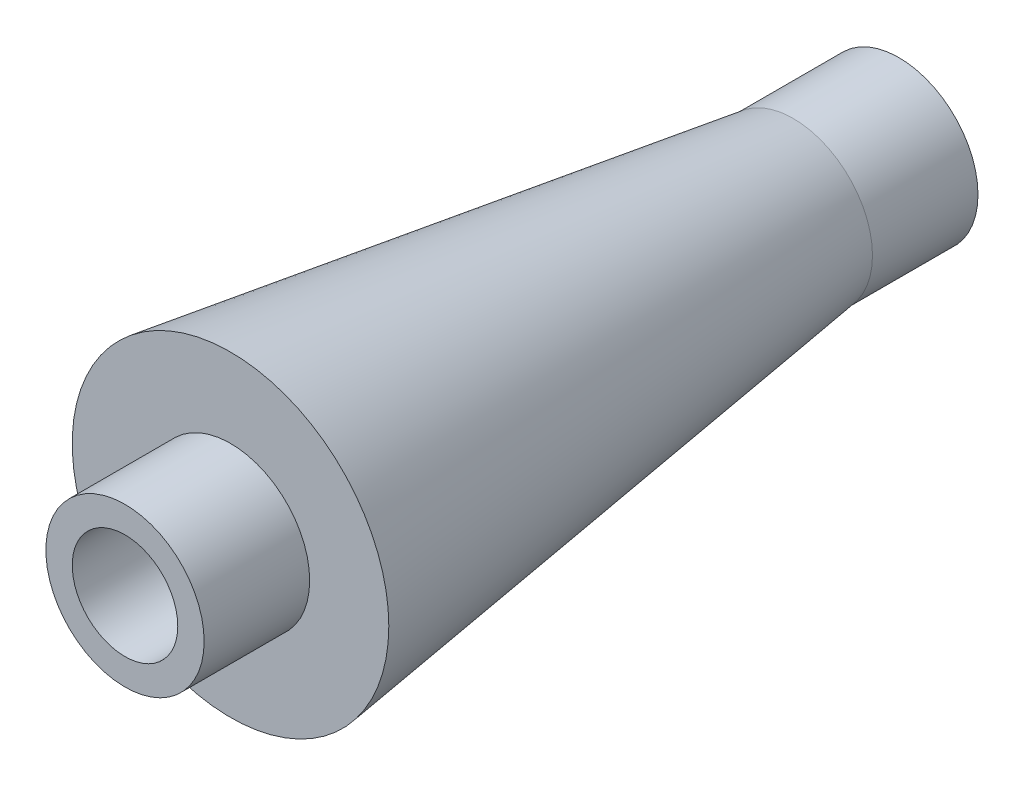
SolidWorks part; units mm, degrees
ref_plane "Front Plane" through (0, 0, 0) normal (0, 0, 1) x (1, 0, 0)
ref_plane "Top Plane" through (0, 0, 0) normal (0, 1, 0) x (1, 0, 0)
ref_plane "Right Plane" through (0, 0, 0) normal (1, 0, 0) x (0, 0, -1)
sketch "Sketch1" plane through (0, 0, 0) normal (0, 1, 0) x (1, 0, 0)
  line L0 (7.1438, 19.05) -> (7.1438, 9.525) construction
  line L1 (7.1438, 9.525) -> (-7.1438, 9.525) construction
  line L2 (14.2875, 19.05) -> (-14.2875, 19.05) construction
  line L3 (7.1437, 79.375) -> (-7.1437, 79.375) construction
  line L4 (7.1438, 69.85) -> (7.1437, 79.375) construction
  line L5 (7.1438, 69.85) -> (14.2875, 19.05) construction
  line L7 (7.1438, 19.05) -> (7.1438, 9.525)
  line L8 (7.1438, 9.525) -> (4.7625, 9.525)
  line L9 (14.2875, 19.05) -> (7.1438, 19.05)
  line L10 (7.1437, 79.375) -> (4.7625, 79.375)
  line L11 (7.1438, 69.85) -> (7.1437, 79.375)
  line L12 (7.1438, 69.85) -> (14.2875, 19.05)
  line L14 (4.7625, -1.5875) -> (4.7625, 92.075) construction
  line L15 (4.7625, 9.525) -> (4.7625, 79.375)
  line L16 (0, -1.5875) -> (0, 92.075) construction
  line L17 (0, -1.5875) -> (0, 92.075)
revolve "Revolve1" add sketch "Sketch1" angle 360 about L17 region at (7.8167, 0, -40.0326)
